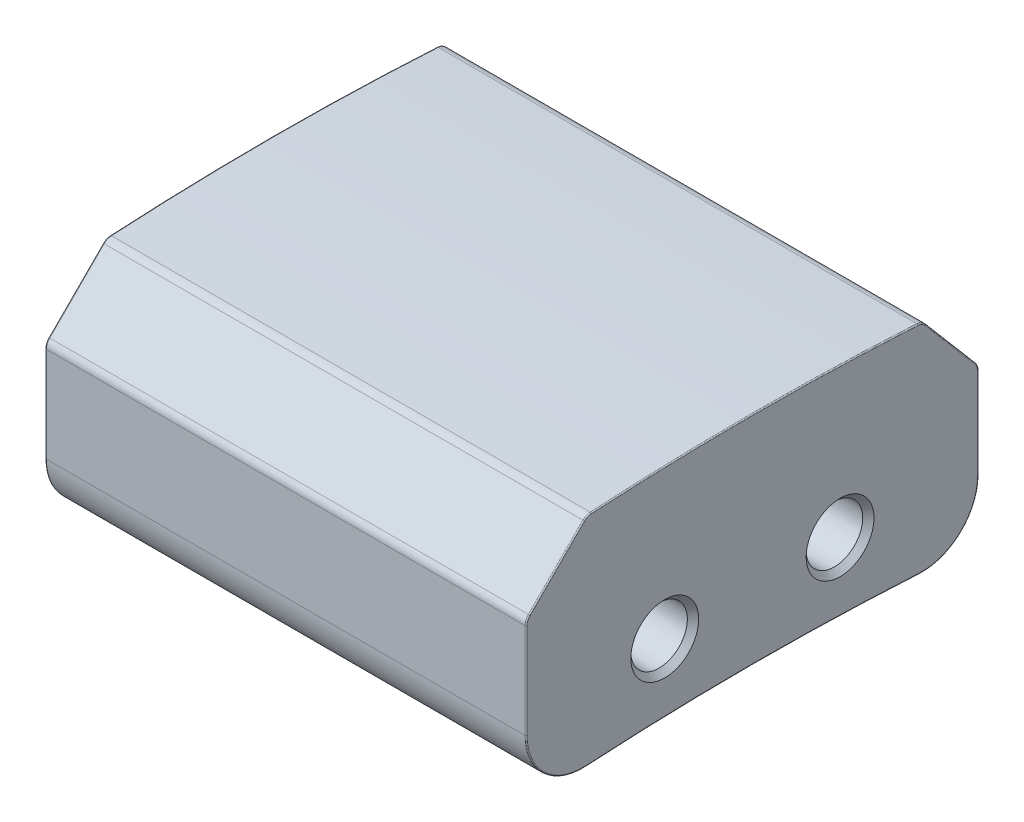
SolidWorks part; units mm, degrees
ref_plane "Front Plane" through (0, 0, 0) normal (0, 0, 1) x (1, 0, 0)
ref_plane "Top Plane" through (0, 0, 0) normal (0, 1, 0) x (1, 0, 0)
ref_plane "Right Plane" through (0, 0, 0) normal (1, 0, 0) x (0, 0, -1)
sketch "Sketch1" plane through (0, 0, 0) normal (0, 1, 0) x (1, 0, 0)
  line L0 (0, -55) -> (0, 55) construction
  line L1 (-4.25, 4) -> (4.25, 4)
  line L2 (-4.25, 4) -> (-4.25, -4)
  line L3 (-4.25, -4) -> (4.25, -4)
  line L4 (4.25, 4) -> (4.25, -4)
  line L5 (-55, 0) -> (55, 0) construction
  dimension "D1" = 8.5
  dimension "D2" = 4.25
  dimension "D3" = 8
  dimension "D4" = 4
extrude "Boss-Extrude1" add sketch "Sketch1" along normal blind 4.2
sketch "Sketch2" plane through (4.25, 0, 0) normal (1, 0, 0) x (0, 0, -1)
  line L0 (55, 0) -> (-55, 0) construction
  line L1 (-4, 4.2) -> (-4, 0) construction
  line L2 (4, 4.2) -> (4, 0) construction
  line L3 (-4, 4.2) -> (4, 4.2) construction
  line L4 (-4, 3.9) -> (-5.2535, 5.2417)
  line L5 (-5.2535, 5.2417) -> (3.8892, 7.1412)
  line L6 (3.8892, 7.1412) -> (5.6792, 5.0772)
  line L7 (5.6792, 5.0772) -> (4, 3.9)
  line L8 (4.7174, 0) -> (0, -2.9048)
  line L9 (0, -2.9048) -> (-4.7004, 0)
  arc A0 (-4.7004, 0) -> (4.7174, 0) centre (0.0085, -49.7778) cw
  arc A1 (-4, 3.9) -> (4, 3.9) centre (0, -45.9397) cw
  dimension "D3" = 50
  dimension "D4" = 50
  dimension "D1" = 0.3
  dimension "D2" = 0.3
extrude "Cut-Extrude1" cut sketch "Sketch2" against normal blind 14.2
chamfer "Chamfer1" distance 1 angle 45 2 edges at (0, 3.9, -4) (0, 3.9, 4) first distance on face at (0, 3.9801, 0) first distance on face at (0, 1.9806, 4)
fillet "Fillet1" radius 1 2 edges at (0, 0.0613, 4) (0, 0.0627, -4)
fillet "Fillet2" radius 0.2 4 edges at (0, 2.8092, -4) (0, 3.9694, -3.0122) (0, 3.9746, 2.9254) (0, 2.9, 4)
fillet "Fillet3" radius 0.02 24 edges at (-4.25, 3.9539, -3.0043) (-4.25, 4.0602, -0.0389) (-4.25, 3.9619, 2.9196) (-4.25, 3.4397, 3.4603) (-4.25, 2.8937, 3.9848) (-4.25, 1.9753, 4) (-4.25, 0.4058, 3.6859) (-4.25, 0.2222, -0.0002) (-4.25, 0.4069, -3.6861) (-4.25, 1.935, -4) (-4.25, 2.8047, -3.9877) (-4.25, 3.3849, -3.5099) (4.25, 0.4069, -3.6861) (4.25, 0.2222, -0.0002) (4.25, 0.4058, 3.6859) (4.25, 1.9753, 4) (4.25, 2.8937, 3.9848) (4.25, 3.4397, 3.4603) (4.25, 3.9619, 2.9196) (4.25, 4.0602, -0.0389) (4.25, 3.9539, -3.0043) (4.25, 3.3849, -3.5099) (4.25, 2.8047, -3.9877) (4.25, 1.935, -4)
sketch "Sketch3" plane through (-4.25, 0, 0) normal (-1, 0, 0) x (0, 0, 1)
  line L0 (4.4, 0) -> (-4.4, 0) construction
  line L1 (0, -2.1598) -> (0, 2.1598) construction
  circle A0 centre (-1.55, 1.4) radius 0.5
  circle A1 centre (1.55, 1.4) radius 0.5
  dimension "D1" = 1
  dimension "D2" = 1
  dimension "D3" = 1.4
  dimension "D4" = 1.4
  dimension "D5" = 1.55
  dimension "D6" = 1.55
extrude "Cut-Extrude2" cut sketch "Sketch3" against normal blind 14.2
chamfer "Chamfer2" distance 0.1 angle 45 4 edges at (4.25, 1.4, -1.05) (4.25, 1.4, 2.05) (-4.25, 1.4, -1.05) (-4.25, 1.4, 2.05)
